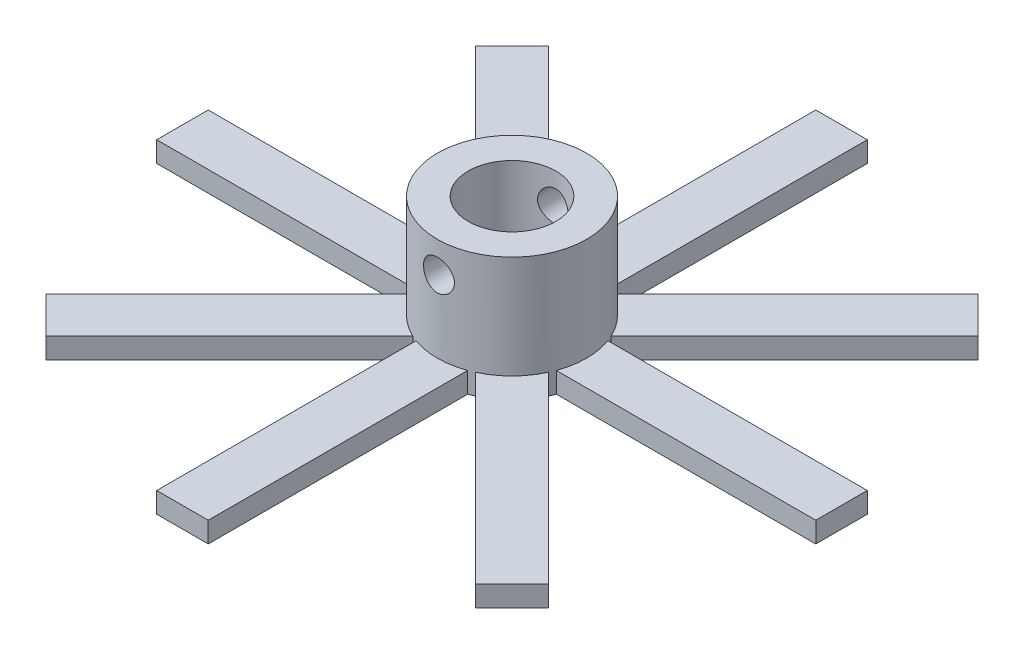
SolidWorks part; units mm, degrees
ref_plane "Front Plane" through (0, 0, 0) normal (0, 0, 1) x (1, 0, 0)
ref_plane "Top Plane" through (0, 0, 0) normal (0, 1, 0) x (1, 0, 0)
ref_plane "Right Plane" through (0, 0, 0) normal (1, 0, 0) x (0, 0, -1)
sketch "Sketch1" plane through (0, 0, 0) normal (0, 1, 0) x (1, 0, 0)
  line L0 (-1.7678, 1.7678) -> (20.8597, 24.3952)
  line L1 (-2.5, 0) -> (2.5, 0)
  line L2 (-2.5, 0) -> (-2.5, 32)
  line L3 (-2.5, 32) -> (2.5, 32)
  line L4 (2.5, 0) -> (2.5, 32)
  line L5 (-1.7678, 1.7678) -> (1.7678, -1.7678)
  line L6 (1.7678, -1.7678) -> (24.3952, 20.8597)
  line L7 (20.8597, 24.3952) -> (24.3952, 20.8597)
  line L8 (0, 2.5) -> (32, 2.5)
  line L9 (0, 2.5) -> (0, -2.5)
  line L10 (0, -2.5) -> (32, -2.5)
  line L11 (32, 2.5) -> (32, -2.5)
  line L12 (1.7678, 1.7678) -> (24.3952, -20.8597)
  line L13 (1.7678, 1.7678) -> (-1.7678, -1.7678)
  line L14 (-1.7678, -1.7678) -> (20.8597, -24.3952)
  line L15 (24.3952, -20.8597) -> (20.8597, -24.3952)
  line L16 (2.5, 0) -> (2.5, -32)
  line L17 (2.5, 0) -> (-2.5, 0)
  line L18 (-2.5, 0) -> (-2.5, -32)
  line L19 (2.5, -32) -> (-2.5, -32)
  line L20 (1.7678, -1.7678) -> (-20.8597, -24.3952)
  line L21 (1.7678, -1.7678) -> (-1.7678, 1.7678)
  line L22 (-1.7678, 1.7678) -> (-24.3952, -20.8597)
  line L23 (-20.8597, -24.3952) -> (-24.3952, -20.8597)
  line L24 (0, -2.5) -> (-32, -2.5)
  line L25 (0, -2.5) -> (0, 2.5)
  line L26 (0, 2.5) -> (-32, 2.5)
  line L27 (-32, -2.5) -> (-32, 2.5)
  line L28 (-1.7678, -1.7678) -> (-24.3952, 20.8597)
  line L29 (-1.7678, -1.7678) -> (1.7678, 1.7678)
  line L30 (1.7678, 1.7678) -> (-20.8597, 24.3952)
  line L31 (-24.3952, 20.8597) -> (-20.8597, 24.3952)
  circle A0 centre (0, 0) radius 4.25
  circle A1 centre (0, 0) radius 7.25
  point P39 (0, 0)
  dimension "D1" = 8.5
  dimension "D4" = 3
  dimension "D2" = 5
  dimension "D3" = 2.5
  dimension "D5" = 32
  dimension "D6" = 32
  dimension "D7" = 8
extrude "Boss-Extrude1" add sketch "Sketch1" along normal blind 2 contours A1 L26 L27 L24 | A1 L22 L23 L20 | A1 L18 L19 L16 | A1 L14 L15 L12 | A1 L10 L11 L8 | A1 L6 L7 L0 | A1 L4 L3 L2 | A1 L30 L31 L28 | A1 | A0 region at (13.825, 0, -13.825) region at (0, 0, -19.5515) region at (-13.825, 0, -13.825) region at (-19.5515, 0, 0) region at (-13.825, 0, 13.825) region at (19.5515, 0, 0) region at (0, 0, 19.5515) region at (13.825, 0, 13.825)
extrude "Boss-Extrude2" add sketch "Sketch1<3>" along normal blind 12 contours A1 | A0
sketch "Sketch1<3>" plane through (0, 0, 0) normal (0, 1, 0) x (1, 0, 0) same geometry as "Sketch1"
sketch "Sketch2" plane through (0, 0, 0) normal (0, 0, 1) x (1, 0, 0)
  line L0 (7.25, 12) -> (-7.25, 12) construction
  circle A0 centre (0, 9) radius 1.5
  dimension "D1" = 3
  dimension "D2" = 3
extrude "Cut-Extrude1" cut sketch "Sketch2" against normal through all both and the other way through all
